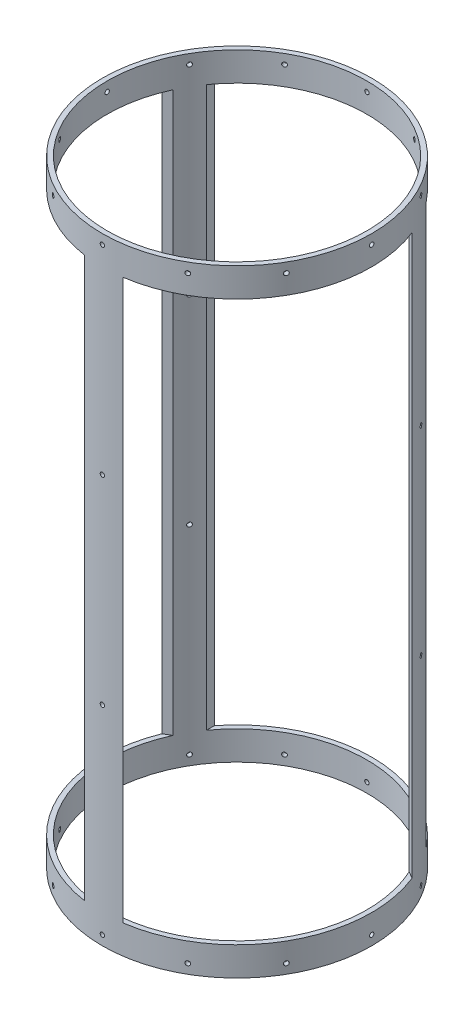
SolidWorks part; units mm, degrees
material "6061-T6 (SS)"
ref_plane "Front Plane" through (0, 0, 0) normal (0, 0, 1) x (1, 0, 0)
ref_plane "Top Plane" through (0, 0, 0) normal (0, 1, 0) x (1, 0, 0)
ref_plane "Right Plane" through (0, 0, 0) normal (1, 0, 0) x (0, 0, -1)
sketch "Sketch1" plane through (0, 0, 0) normal (0, 1, 0) x (1, 0, 0)
  circle A0 centre (0, 0) radius 88.9
  circle A1 centre (0, 0) radius 85.725
  dimension "D1" = 177.8
  dimension "D2" = 171.45
extrude "Boss-Extrude1" add sketch "Sketch1" along normal mid plane 407.162
sketch "Sketch2" plane through (0, 0, 0) normal (0, 0, 1) x (1, 0, 0)
  line L0 (85.725, 203.581) -> (-85.725, 203.581) construction
  line L1 (-69.85, -184.531) -> (69.85, -184.531)
  line L2 (-69.85, -184.531) -> (-69.85, 184.531)
  line L3 (-69.85, 184.531) -> (69.85, 184.531)
  line L4 (69.85, -184.531) -> (69.85, 184.531)
  line L5 (-69.85, -184.531) -> (69.85, 184.531) construction
  line L6 (-69.85, 184.531) -> (69.85, -184.531) construction
  line L7 (88.9, -203.581) -> (88.9, 203.581) construction
  point P0 (0, 0)
  dimension "D1" = 19.05
  dimension "D2" = 19.05
extrude "Cut-Extrude1" cut sketch "Sketch2" against normal up to surface (54.9926 mm away) up to face at (0, 203.581, 88.9)
pattern_circular "CirPattern1" count 3 over 360 about axis through (0, 203.581, 0) along (0, -1, 0) of "Cut-Extrude1"
ref_plane "Plane1" through (88.9, 0, 0) normal (1, 0, 0) x (0, 0, -1)
sketch "Sketch4" plane through (88.9, 0, 0) normal (1, 0, 0) x (0, 0, -1)
  line L0 (0, 97.79) -> (0, -97.79) construction
  line L1 (88.9, 203.581) -> (-88.9, 203.581) construction
  circle A0 centre (0, 197.231) radius 1.4351
  dimension "D1" = 2.8702
  dimension "D2" = 6.35
extrude "Cut-Extrude3" cut sketch "Sketch4" against normal blind 15.24
pattern_circular "CirPattern3" count 12 over 360 about axis through (0, 203.581, 0) along (0, -1, 0) of "Cut-Extrude3"
mirror "Mirror1" about plane through (0, 0, 0) normal (0, 1, 0) of "Cut-Extrude3", "CirPattern3"
ref_plane "Plane2" through (0, 0, 88.9) normal (0, 0, 1) x (1, 0, 0)
sketch "Sketch5" plane through (0, 0, 88.9) normal (0, 0, 1) x (1, 0, 0)
  circle A0 centre (0, -65.7606) radius 1.4351
  circle A1 centre (0, 65.7606) radius 1.4351
  circle A2 centre (0, 197.231) radius 1.4351 construction
  circle A3 centre (0, -197.231) radius 1.4351 construction
  dimension "D1" = 131.4704
  dimension "D2" = 131.4704
  dimension "D3" = 2.8702
  dimension "D4" = 2.8702
extrude "Cut-Extrude4" cut sketch "Sketch5" against normal blind 46.482
pattern_circular "CirPattern4" count 3 over 360 about axis through (0, 203.581, 0) along (0, -1, 0) of "Cut-Extrude4"
